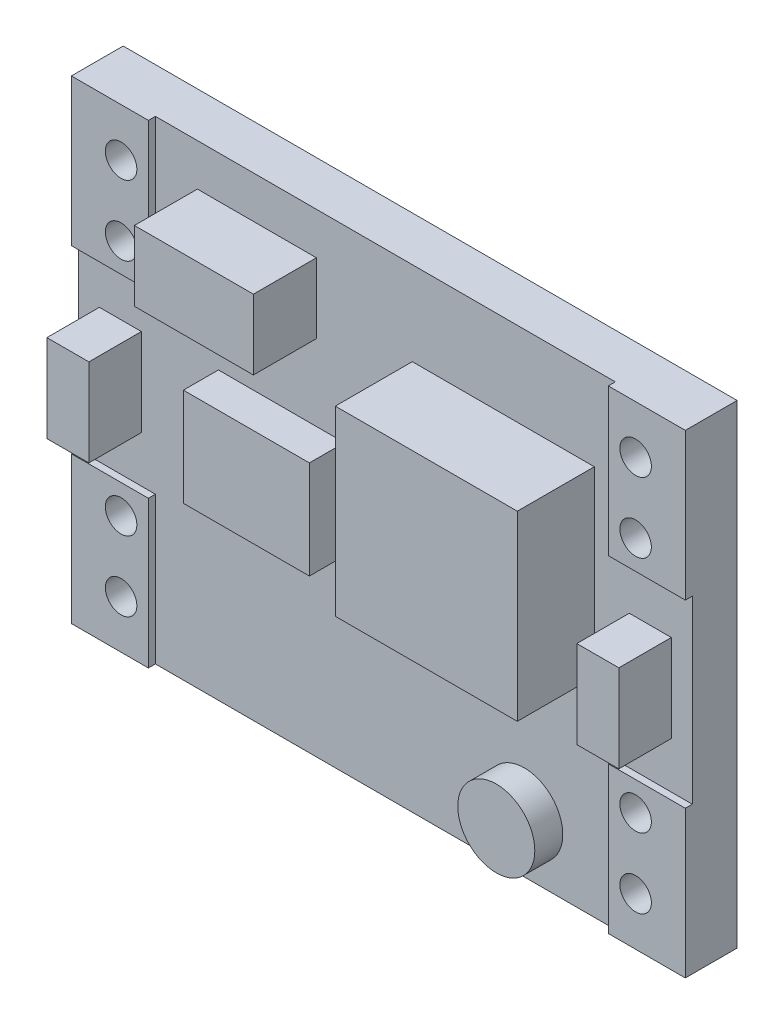
SolidWorks part; units mm, degrees
ref_plane "Front Plane" through (0, 0, 0) normal (0, 0, 1) x (1, 0, 0)
ref_plane "Top Plane" through (0, 0, 0) normal (0, 1, 0) x (1, 0, 0)
ref_plane "Right Plane" through (0, 0, 0) normal (1, 0, 0) x (0, 0, -1)
sketch "Sketch1" plane through (0, 0, 0) normal (0, 0, 1) x (1, 0, 0)
  line L1 (0, 0) -> (22.2758, 0)
  line L2 (0, 0) -> (0, 17.2085)
  line L3 (0, 17.2085) -> (22.2758, 17.2085)
  line L4 (22.2758, 0) -> (22.2758, 17.2085)
  dimension "D1" = 17.2085
  dimension "D2" = 22.2758
extrude "Boss-Extrude1" add sketch "Sketch1" along normal blind 1.6256
sketch "Sketch2" plane through (0, 0, 1.6256) normal (0, 0, 1) x (1, 0, 0)
  line L0 (1.8034, 15.4623) -> (1.8034, 12.9223) construction
  line L1 (0, 8.6042) -> (22.2758, 8.6042) construction
  line L2 (0, 17.2085) -> (0, 0) construction
  line L3 (22.2758, 0) -> (22.2758, 17.2085) construction
  line L4 (11.1379, 8.6042) -> (11.1379, 17.2085) construction
  line L5 (22.2758, 17.2085) -> (0, 17.2085) construction
  line L6 (1.8034, 15.4623) -> (20.4724, 15.4622) construction
  line L7 (20.4724, 15.4622) -> (20.4724, 12.9223) construction
  line L8 (1.8034, 4.2862) -> (1.8034, 1.7462) construction
  line L9 (20.4724, 1.7462) -> (20.4724, 4.2862) construction
  line L10 (1.8034, 1.7462) -> (20.4724, 1.7462) construction
  circle A0 centre (1.8034, 15.4623) radius 0.5715
  circle A1 centre (1.8034, 12.9223) radius 0.5715
  circle A2 centre (20.4724, 15.4622) radius 0.5715
  circle A3 centre (20.4724, 12.9223) radius 0.5715
  circle A4 centre (20.4724, 4.2862) radius 0.5715
  circle A5 centre (20.4724, 1.7462) radius 0.5715
  circle A6 centre (1.8034, 4.2862) radius 0.5715
  circle A7 centre (1.8034, 1.7462) radius 0.5715
  dimension "D1" = 1.143
  dimension "D2" = 18.669
  dimension "D3" = 2.54
  dimension "D4" = 13.716
extrude "Cut-Extrude1" cut sketch "Sketch2" against normal through all
sketch "Sketch3" plane through (0, 0, 1.6256) normal (0, 0, 1) x (1, 0, 0)
  line L0 (22.2758, 0) -> (22.2758, 17.2085) construction
  line L1 (0.762, 10.1917) -> (2.286, 10.1917)
  line L2 (0.762, 10.1917) -> (0.762, 7.0167)
  line L3 (0.762, 7.0167) -> (2.286, 7.0167)
  line L4 (2.286, 10.1917) -> (2.286, 7.0167)
  line L5 (19.9898, 10.1917) -> (21.5138, 10.1917)
  line L6 (19.9898, 10.1917) -> (19.9898, 7.0167)
  line L7 (19.9898, 7.0167) -> (21.5138, 7.0167)
  line L8 (21.5138, 10.1917) -> (21.5138, 7.0167)
  line L9 (4.318, 15.6845) -> (8.636, 15.6845)
  line L10 (4.318, 15.6845) -> (4.318, 13.1445)
  line L11 (4.318, 13.1445) -> (8.636, 13.1445)
  line L12 (8.636, 15.6845) -> (8.636, 13.1445)
  line L13 (5.08, 10.3822) -> (9.652, 10.3822)
  line L14 (5.08, 10.3822) -> (5.08, 6.8262)
  line L15 (5.08, 6.8262) -> (9.652, 6.8262)
  line L16 (9.652, 10.3822) -> (9.652, 6.8262)
  line L17 (12.1158, 14.1605) -> (18.7198, 14.1605)
  line L18 (12.1158, 14.1605) -> (12.1158, 7.5565)
  line L19 (12.1158, 7.5565) -> (18.7198, 7.5565)
  line L20 (18.7198, 14.1605) -> (18.7198, 7.5565)
  line L22 (0, 0) -> (22.2758, 0) construction
  line L23 (21.5138, 8.6042) -> (22.2758, 8.6042) construction
  line L24 (0.762, 8.6042) -> (0, 8.6042) construction
  line L25 (0, 17.2085) -> (0, 0) construction
  line L26 (2.286, 8.6042) -> (5.08, 8.6042) construction
  line L27 (22.2758, 17.2085) -> (0, 17.2085) construction
  circle A0 centre (16.1798, 2.032) radius 1.397
  point P36 (18.7198, 15.065)
  dimension "D11" = 2.794
  dimension "D1" = 1.524
  dimension "D2" = 3.175
  dimension "D3" = 3.175
  dimension "D4" = 1.524
  dimension "D5" = 4.318
  dimension "D6" = 2.54
  dimension "D7" = 6.604
  dimension "D8" = 6.604
  dimension "D9" = 3.556
  dimension "D10" = 4.572
  dimension "D12" = 6.096
  dimension "D13" = 2.032
  dimension "D14" = 0.762
  dimension "D15" = 0.762
  dimension "D16" = 5.08
  dimension "D17" = 1.524
  dimension "D18" = 4.318
  dimension "D19" = 3.556
  dimension "D20" = 3.048
extrude "Boss-Extrude2" add sketch "Sketch3" along normal blind 1.905 contours L1 L4 L3 L2 | L5 L8 L7 L6
extrude "Boss-Extrude3" add sketch "Sketch3<3>" along normal blind 2.286 contours L11 L12 L9 L10
sketch "Sketch3<3>" plane through (0, 0, 1.6256) normal (0, 0, 1) x (1, 0, 0) same geometry as "Sketch3"
extrude "Boss-Extrude4" add sketch "Sketch3<4>" along normal blind 1.27 contours L15 L16 L13 L14
sketch "Sketch3<4>" plane through (0, 0, 1.6256) normal (0, 0, 1) x (1, 0, 0) same geometry as "Sketch3"
extrude "Boss-Extrude5" add sketch "Sketch3<5>" along normal blind 2.794 contours L19 L20 L17 L18
sketch "Sketch3<5>" plane through (0, 0, 1.6256) normal (0, 0, 1) x (1, 0, 0) same geometry as "Sketch3"
extrude "Boss-Extrude6" add sketch "Sketch3<6>" along normal blind 1.016 contours A0
sketch "Sketch3<6>" plane through (0, 0, 1.6256) normal (0, 0, 1) x (1, 0, 0) same geometry as "Sketch3"
sketch "Sketch4" plane through (0, 0, 1.6256) normal (0, 0, 1) x (1, 0, 0)
  line L1 (0, 17.2085) -> (2.794, 17.2085)
  line L2 (0, 17.2085) -> (0, 11.8745)
  line L3 (0, 11.8745) -> (2.794, 11.8745)
  line L4 (2.794, 17.2085) -> (2.794, 11.8745)
  line L5 (0, 0) -> (2.794, 0)
  line L6 (0, 0) -> (0, 5.334)
  line L7 (0, 5.334) -> (2.794, 5.334)
  line L8 (2.794, 0) -> (2.794, 5.334)
  line L9 (22.2758, 0) -> (19.4818, 0)
  line L10 (22.2758, 0) -> (22.2758, 5.334)
  line L11 (22.2758, 5.334) -> (19.4818, 5.334)
  line L12 (19.4818, 0) -> (19.4818, 5.334)
  line L13 (22.2758, 17.2085) -> (19.4818, 17.2085)
  line L14 (22.2758, 17.2085) -> (22.2758, 11.8745)
  line L15 (22.2758, 11.8745) -> (19.4818, 11.8745)
  line L16 (19.4818, 17.2085) -> (19.4818, 11.8745)
  circle A0 centre (20.4724, 15.4622) radius 0.5715 construction
  circle A1 centre (20.4724, 12.9223) radius 0.5715 construction
  circle A2 centre (20.4724, 4.2862) radius 0.5715 construction
  circle A3 centre (20.4724, 1.7462) radius 0.5715 construction
  circle A4 centre (1.8034, 1.7462) radius 0.5715 construction
  circle A5 centre (1.8034, 4.2862) radius 0.5715 construction
  circle A6 centre (1.8034, 12.9223) radius 0.5715 construction
  circle A7 centre (1.8034, 15.4623) radius 0.5715 construction
  circle A8 centre (20.4724, 15.4622) radius 0.5715
  circle A9 centre (20.4724, 12.9223) radius 0.5715
  circle A10 centre (20.4724, 4.2862) radius 0.5715
  circle A11 centre (20.4724, 1.7462) radius 0.5715
  circle A12 centre (1.8034, 1.7462) radius 0.5715
  circle A13 centre (1.8034, 4.2862) radius 0.5715
  circle A14 centre (1.8034, 12.9223) radius 0.5715
  circle A15 centre (1.8034, 15.4623) radius 0.5715
  dimension "D1" = 5.334
  dimension "D2" = 2.794
  dimension "D3" = 2.794
  dimension "D4" = 5.334
  dimension "D5" = 5.334
  dimension "D6" = 2.794
  dimension "D7" = 2.794
  dimension "D8" = 5.334
extrude "Boss-Extrude7" add sketch "Sketch4" along normal blind 0.254
